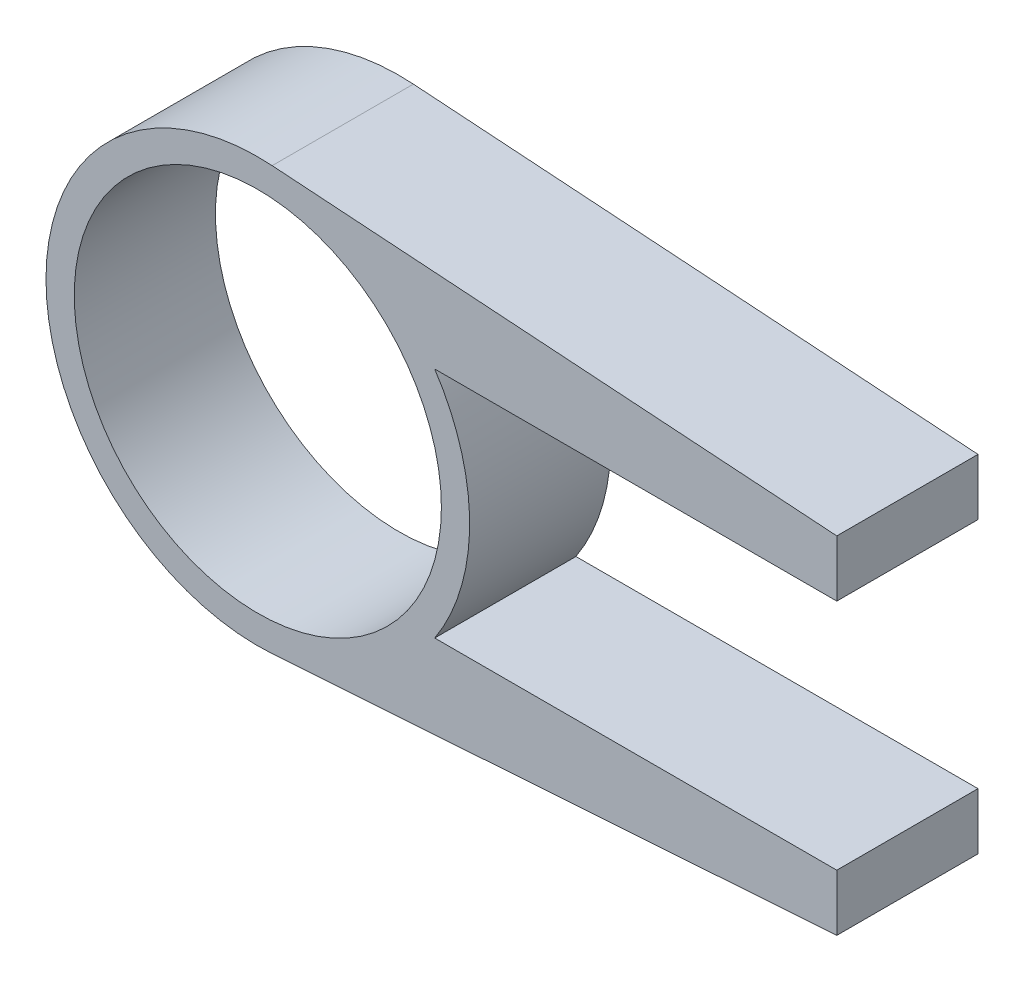
SolidWorks part; units mm, degrees
ref_plane "Front Plane" through (0, 0, 0) normal (0, 0, 1) x (1, 0, 0)
ref_plane "Top Plane" through (0, 0, 0) normal (0, 1, 0) x (1, 0, 0)
ref_plane "Right Plane" through (0, 0, 0) normal (1, 0, 0) x (0, 0, -1)
sketch "Sketch1" plane through (0, 0, 0) normal (0, 0, 1) x (1, 0, 0)
  line L0 (-164.3342, 0) -> (204.2426, 0) construction
  line L1 (79.5494, -52.3875) -> (260.35, -52.3875)
  line L2 (6.4541, 95.0311) -> (260.35, 77.7875)
  line L3 (0, 121.6596) -> (0, -46.3375) construction
  line L4 (79.5494, 52.3875) -> (260.35, 52.3875)
  line L5 (260.35, 91.3401) -> (260.35, -89.9495) construction
  line L6 (260.35, 52.3875) -> (260.35, 77.7875)
  line L8 (260.35, -52.3875) -> (260.35, -77.7875)
  line L9 (6.4541, -95.0311) -> (260.35, -77.7875)
  arc A0 (6.4541, 95.0311) -> (6.4541, -95.0311) centre (0, 0) ccw
  arc A3 (79.5494, -52.3875) -> (79.5494, 52.3875) centre (0, 0) ccw
  point P20 (0, 0)
  point P22 (0, 0)
  point P23 (0, 0)
  point P24 (0, 0)
  point P25 (0, 0)
  point P26 (0, 0)
  dimension "D1" = 190.5
  dimension "D3" = 52.3875
  dimension "D4" = 52.3875
  dimension "D5" = 260.35
  dimension "D6" = 260.35
  dimension "D7" = 25.4
  dimension "D9" = 25.4
extrude "Boss-Extrude2" add sketch "Sketch1" along normal blind 31.75 and the other way blind 31.75
sketch "Sketch2" plane through (0, 0, 31.75) normal (0, 0, 1) x (1, 0, 0)
  circle A0 centre (0, 0) radius 82.55
  point P2 (0, 0)
  dimension "D1" = 165.1
extrude "Cut-Extrude3" cut sketch "Sketch2" against normal up to next
